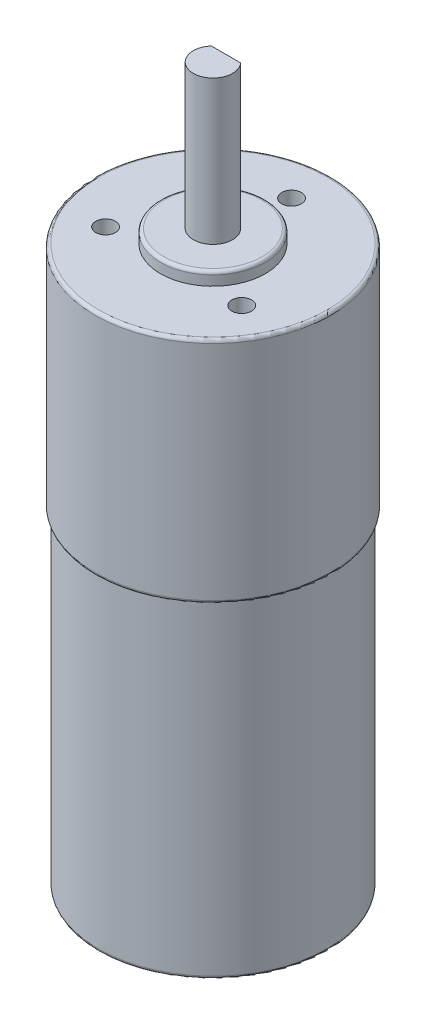
SolidWorks part; units mm, degrees
ref_plane "前视基准面" through (0, 0, 0) normal (0, 0, 1) x (1, 0, 0)
ref_plane "上视基准面" through (0, 0, 0) normal (0, 1, 0) x (1, 0, 0)
ref_plane "右视基准面" through (0, 0, 0) normal (1, 0, 0) x (0, 0, -1)
sketch "草图1" plane through (0, 0, 0) normal (0, 1, 0) x (1, 0, 0)
  circle A0 centre (0, 0) radius 17.5
  dimension "D1" = 35
extrude "凸台-拉伸1" add sketch "草图1" along normal blind 50
sketch "草图2" plane through (0, 50, 0) normal (0, 1, 0) x (1, 0, 0)
  circle A0 centre (0, 0) radius 17.5
sketch "草图3" plane through (0, 50, 0) normal (0, 1, 0) x (1, 0, 0)
  circle A0 centre (0, 0) radius 18
  dimension "D1" = 36
extrude "凸台-拉伸4" add sketch "草图3" along normal blind 35
sketch "草图4" plane through (0, 85, 0) normal (0, 1, 0) x (1, 0, 0)
  circle A0 centre (0, 0) radius 8
  dimension "D1" = 16
extrude "凸台-拉伸5" add sketch "草图4" along normal blind 2
sketch "草图5" plane through (0, 87, 0) normal (0, 1, 0) x (1, 0, 0)
  circle A0 centre (0, 0) radius 3
  dimension "D1" = 6
extrude "凸台-拉伸6" add sketch "草图5" along normal blind 22
sketch "草图6" plane through (0, 85, 0) normal (0, 1, 0) x (1, 0, 0)
  circle A0 centre (0, 12) radius 1.5
  circle A1 centre (10.3923, -6) radius 1.5
  circle A2 centre (-10.3923, -6) radius 1.5
  point P5 (0, 0)
  point P10 (0, 0)
  point P12 (0, 0)
  point P14 (0, 0)
  dimension "D1" = 3
  dimension "D2" = 12
  dimension "D3" = 3
extrude "切除-拉伸1" cut sketch "草图6" against normal blind 5
sketch "草图7" plane through (0, 109, 0) normal (0, 1, 0) x (1, 0, 0)
  line L1 (-4.4458, 3.719) -> (3.6159, 3.719)
  line L2 (-4.4458, 3.719) -> (-4.4458, 2)
  line L3 (-4.4458, 2) -> (3.6159, 2)
  line L4 (3.6159, 3.719) -> (3.6159, 2)
  dimension "D1" = 2
extrude "切除-拉伸2" cut sketch "草图7" against normal blind 18
fillet "圆角10" radius 0.5 1 edges at (0, 85, 18)
fillet "圆角11" radius 0.5 1 edges at (0, 50, 18)
fillet "圆角12" radius 0.5 1 edges at (0, 0, 17.5)
fillet "圆角13" radius 0.5 1 edges at (0, 87, 8)
